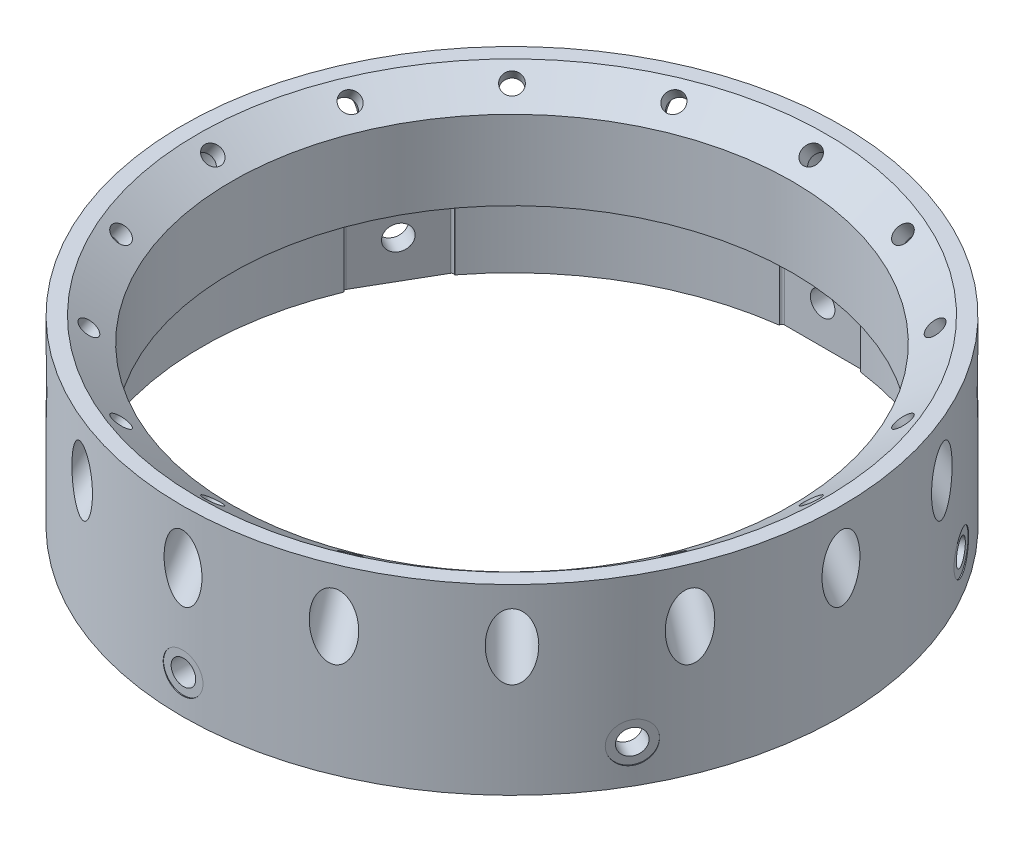
SolidWorks part; units mm, degrees
material "6061-T6 (SS)"
ref_plane "Front Plane" through (0, 0, 0) normal (0, 0, 1) x (1, 0, 0)
ref_plane "Top Plane" through (0, 0, 0) normal (0, 1, 0) x (1, 0, 0)
ref_plane "Right Plane" through (0, 0, 0) normal (1, 0, 0) x (0, 0, -1)
sketch "Main sketch" plane through (0, 0, 0) normal (0, 0, 1) x (1, 0, 0)
  line L0 (0, 0) -> (-87, 0) construction
  line L23 (-87, 0) -> (-87, 27.1992)
  line L24 (-83, 27.1992) -> (-74, 20.8973)
  line L25 (-74, 20.8973) -> (-74, 0)
  line L26 (-74, 0) -> (-81, 0)
  line L30 (0, 0) -> (0, -35.5238) construction
  line L31 (-87, 27.1992) -> (-83, 27.1992)
  line L32 (-74, 20.8973) -> (-87, 20.8973) construction
  line L33 (-87, 0) -> (-87, -21)
  line L34 (-87, -21) -> (-82, -21)
  line L35 (-82, -21) -> (-82, 0)
  line L36 (-82, 0) -> (-81, 0)
  point P4 (-87, 30)
  dimension "D1" = 87
  dimension "D4" = 55
  dimension "D5" = 30
  dimension "D6" = 13
  dimension "D8" = 4
  dimension "D9" = 90
revolve "Main revolve" add sketch "Main sketch" angle 360 about L30
sketch "Hole position" plane through (0, 0, 0) normal (0, 0, 1) x (1, 0, 0)
  line L0 (-79, 24.3983) -> (-83, 18.6857) construction
  line L1 (-83, 27.1992) -> (-74, 20.8973) construction
  line L2 (0, 30) -> (0, -2.3509) construction
  line L4 (-83, 27.1992) -> (-83, -10.9444) construction
  line L6 (87, 30) -> (-87, 30) construction
  line L7 (-83, 18.6857) -> (-67.2656, 7.6684) construction
  point P7 (-79, 24.3983)
  dimension "D1" = 4
ref_plane "Hole plane" through (-18.5267, -26.4589, 0) normal (-0.5736, -0.8192, 0) x (0.8192, -0.5736, 0)
sketch "Sketch14" plane through (-18.5267, -26.4589, 0) normal (-0.5736, -0.8192, 0) x (0.8192, -0.5736, 0)
  circle A1 centre (-78.7073, 0) radius 5
  dimension "D1" = 5
extrude "Hole extrude 1" cut sketch "Sketch14" against normal blind 3 and the other way through all
hole_wizard "screw extrude" positions "3DSketch13" profile "Sketch15" hole size "Ø5.0" standard "DIN" end condition up to next
sketch3d "3DSketch13"
  line L0 (-79, 24.3983, 0) -> (-83, 18.6857, 0) construction
  point P0 (-81.2793, 21.1432, 0)
sketch "Sketch15" plane through (-81.2793, 21.1432, 0) normal (0, 0, 1) x (0.8192, -0.5736, 0)
  line L0 (0, 0) -> (0, 3.9738)
  line L1 (0, 3.9738) -> (2.5, 3.9738)
  line L2 (2.5, 3.9738) -> (2.5, 0)
  line L5 (2.5, 0) -> (0, 0)
  line L11 (0, -6.35) -> (0, 107.95) construction
  dimension "Thru Hole Dia." = 5
  dimension "Thru Hole Depth" = 3.9738
pattern_circular "Screw holes pattern" count 16 over 360 about axis through (0, 0, 0) along (0, 1, 0) of "Hole extrude 1", "screw extrude" reverse direction yes
ref_plane "Płaszczyzna1" through (16.9729, 0, 85.3283) normal (0.1951, 0, 0.9808) x (0, 1, 0)
sketch "Szkic14" plane through (0, 0, 0) normal (0, 0, 1) x (1, 0, 0)
  line L0 (0, -21) -> (0, -11)
  line L1 (-87, -21) -> (87, -21) construction
  circle A0 centre (0, -11) radius 3.25
  dimension "D1" = 6.5
extrude "Wytnij-wyciągnięcie3" cut sketch "Szkic14" against normal up to next contours A0 region at (2.2331, -13.2331, 0)
pattern_circular "Szyk kołowy2" count 6 over 360 about axis through (0, -21, 0) along (0, 1, 0) of "Wytnij-wyciągnięcie3"
ref_plane "Plane1" through (0, 0, 87) normal (0, 0, 1) x (1, 0, 0)
sketch "Sketch16" plane through (0, 0, 87) normal (0, 0, 1) x (1, 0, 0)
  circle A0 centre (0, -11) radius 3.25 construction
  circle A1 centre (0, -11) radius 3.25
  circle A2 centre (0, -11) radius 5.25
  dimension "D1" = 10.5
extrude "Cut-Extrude1" cut sketch "Sketch16" against normal blind 0.25
pattern_circular "CirPattern1" count 6 over 360 about axis through (0, 0, 0) along (0, 1, 0) of "Cut-Extrude1"
sketch "Sketch17" plane through (0, -21, 0) normal (0, -1, 0) x (1, 0, 0)
  line L4 (10.1, -80.819) -> (10.1, -82.0164)
  line L6 (0, -82.0164) -> (10.1, -82.0164)
  line L7 (0, -82.0164) -> (-10.1, -82.0164)
  line L8 (10.1, -80.819) -> (0, -80.819)
  line L9 (0, -80.819) -> (-10.1, -80.819)
  line L10 (-10.1, -80.819) -> (-10.1, -82.0164)
extrude "Cut-Extrude2" cut sketch "Sketch17" against normal blind 21
pattern_circular "CirPattern2" count 6 over 360 about axis through (0, 0, 0) along (0, 1, 0) of "Cut-Extrude2"
sketch "Sketch18" plane through (0, 0, -82.0164) normal (0, 0, 1) x (1, 0, 0)
  line L0 (-10.1, -21) -> (-10.72, -21)
  line L1 (-10.72, -21) -> (-10.72, 0)
  line L2 (-10.72, 0) -> (-10.1, 0)
  line L3 (10.1, 0) -> (10.72, 0)
  line L4 (-10.1, -21) -> (10.1, -21)
  line L5 (10.1, -21) -> (10.1, 0)
  line L6 (10.1, 0) -> (-10.1, 0)
  line L7 (-10.1, 0) -> (-10.1, -21)
  line L8 (-10.1, -21) -> (10.1, -21)
  line L9 (10.1, -21) -> (10.1, 0)
  line L10 (10.1, 0) -> (-10.1, 0)
  line L11 (-10.1, 0) -> (-10.1, -21)
  line L12 (10.72, 0) -> (10.72, -21)
  line L13 (10.72, -21) -> (10.1, -21)
  line M8 (10.1, -21) -> (10.1, 0)
  line M10 (-10.1, 0) -> (-10.1, -21)
  dimension "D2" = 0.62
  dimension "D3" = 0.62
  dimension "D1" = 0
extrude "Cut-Extrude3" cut sketch "Sketch18" along normal blind 10 contours L2 L1 L0 M10 | L13 L12 L3 M8 region at (-10.41, -10.5, -82.0164) region at (10.41, -10.5, -82.0164)
fillet "Fillet1" radius 0.62 2 edges at (10.72, -10.5, -82.0164) (-10.72, -10.5, -82.0164)
pattern_circular "CirPattern3" count 6 over 360 about axis through (0, 20.8973, 0) along (0, 1, 0) of "Fillet1", "Cut-Extrude3"
